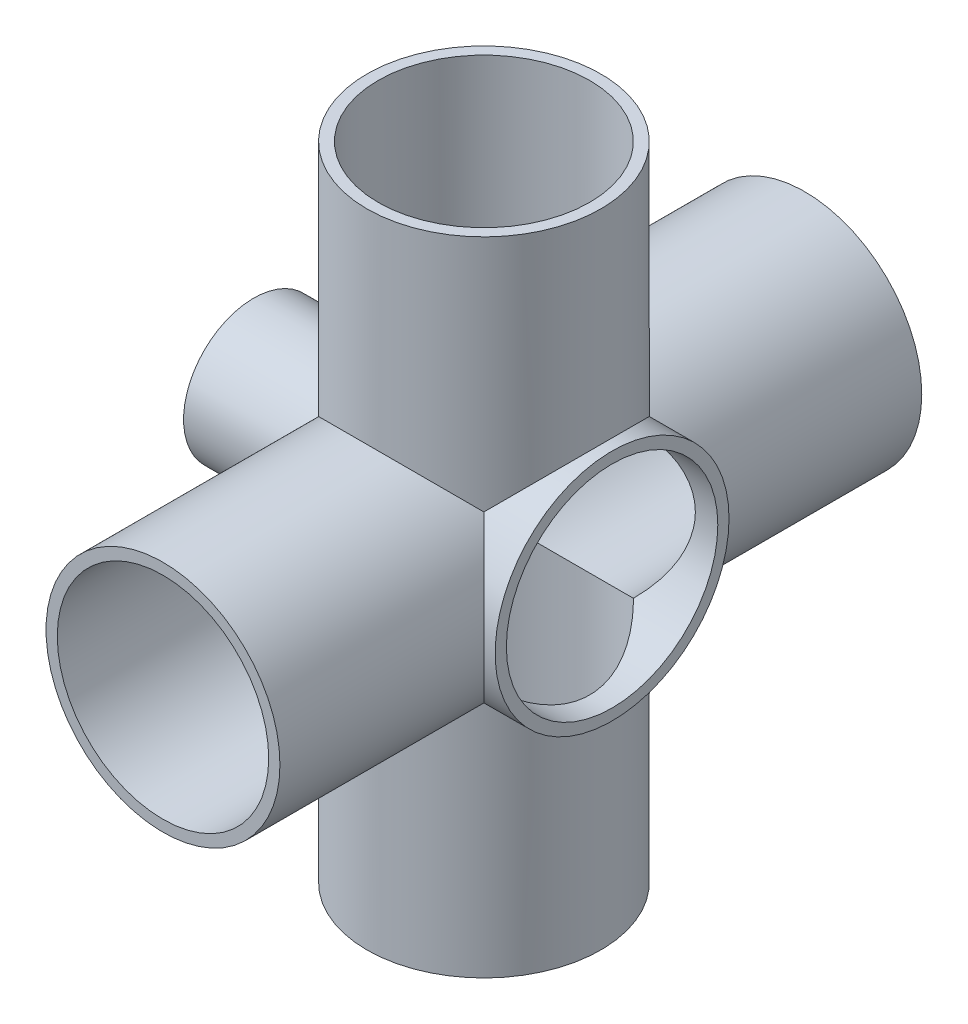
SolidWorks part; units mm, degrees
ref_plane "Front Plane" through (0, 0, 0) normal (0, 0, 1) x (1, 0, 0)
ref_plane "Top Plane" through (0, 0, 0) normal (0, 1, 0) x (1, 0, 0)
ref_plane "Right Plane" through (0, 0, 0) normal (1, 0, 0) x (0, 0, -1)
sketch "Sketch1" plane through (0, 0, 0) normal (0, 1, 0) x (1, 0, 0)
  circle A0 centre (0, 0) radius 31.75
  dimension "D1" = 63.5
extrude "Extrude3" add sketch "Sketch1" along normal blind 87.122 and the other way blind 87.122
sketch "Sketch4" plane through (0, 0, 0) normal (0, 0, 1) x (1, 0, 0)
  circle A0 centre (0, 0) radius 31.75
extrude "Extrude4" add sketch "Sketch4" along normal blind 87.122 and the other way blind 87.122
sketch "Sketch6" plane through (0, 0, 0) normal (1, 0, 0) x (0, 0, -1)
  circle A0 centre (0, 0) radius 31.75
  dimension "D1" = 63.5
extrude "Extrude5" add sketch "Sketch6" along normal blind 34.798
sketch "Sketch7" plane through (0, 0, 0) normal (1, 0, 0) x (0, 0, -1)
  circle A0 centre (0, 0) radius 19.05
extrude "Extrude6" add sketch "Sketch7" against normal blind 62.484
sketch "Sketch9" plane through (0, 0, 0) normal (0, 1, 0) x (1, 0, 0)
  circle A0 centre (0, 0) radius 28.702
  dimension "D1" = 57.404
extrude "Cut-Extrude1" cut sketch "Sketch9" against normal through all and the other way through all
sketch "Sketch10" plane through (0, 0, 0) normal (0, 0, 1) x (1, 0, 0)
  circle A0 centre (0, 0) radius 28.702
  dimension "D1" = 57.404
extrude "Cut-Extrude2" cut sketch "Sketch10" against normal through all and the other way through all
sketch "Sketch11" plane through (0, 0, 0) normal (1, 0, 0) x (0, 0, -1)
  circle A0 centre (0, 0) radius 28.702
  dimension "D1" = 57.404
extrude "Cut-Extrude3" cut sketch "Sketch11" along normal through all
sketch "Sketch12" plane through (0, 0, 0) normal (1, 0, 0) x (0, 0, -1)
  circle A0 centre (0, 0) radius 17.399
  dimension "D1" = 34.798
extrude "Cut-Extrude4" cut sketch "Sketch12" against normal through all
sketch "Sketch13" plane through (0, 0, 0) normal (0, 1, 0) x (1, 0, 0)
  line L0 (0, 0) -> (27.6369, 0)
sketch "Sketch14" plane through (0, 0, 0) normal (0, 0, 1) x (1, 0, 0)
  line L0 (0, 0) -> (0, 23.5006)
sketch "Sketch15" plane through (0, 0, 0) normal (1, 0, 0) x (0, 0, -1)
  line L0 (0, 0) -> (12.1356, 0)
